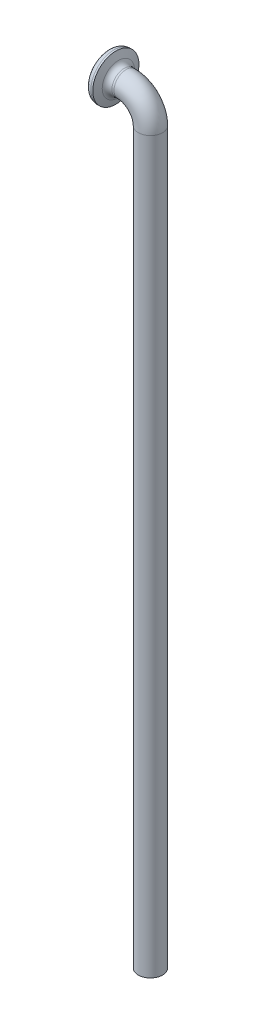
SolidWorks part; units mm, degrees
ref_plane "Front Plane" through (0, 0, 0) normal (0, 0, 1) x (1, 0, 0)
ref_plane "Top Plane" through (0, 0, 0) normal (0, 1, 0) x (1, 0, 0)
ref_plane "Right Plane" through (0, 0, 0) normal (1, 0, 0) x (0, 0, -1)
sketch "Sketch1" plane through (0, 0, 0) normal (0, 0, 1) x (1, 0, 0)
  line L0 (0, 0) -> (0, 60)
  line L1 (-2, 62) -> (-3.5, 62)
  line L2 (-3.5, 63.9) -> (-3.5, 60.1)
  arc A0 (0, 60) -> (-2, 62) centre (-2, 60) ccw
  point P8 (-3.5, 62)
  dimension "D1" = 2
  dimension "D2" = 1.5
  dimension "D3" = 3.8
  dimension "D4" = 60
sweep "Sweep1" add path "Sketch1" circular profile diameter 2 parameters "D3"=2
sketch "Sketch10" plane through (-3.5, 0, 0) normal (-1, 0, 0) x (0, 0, 1)
  circle A0 centre (0, 62) radius 1.9
  dimension "D1" = 3.8
extrude "Boss-Extrude1" add sketch "Sketch10" against normal blind 1.2
chamfer "Chamfer1" distance 1.5 angle 20 1 edges at (-2.3, 60.1, 0) first distance on face at (-2.3, 61, 0)
fillet "Fillet1" radius 0.5 2 edges at (-3.5, 60.1, 0) (-2.5184, 61, 0)
